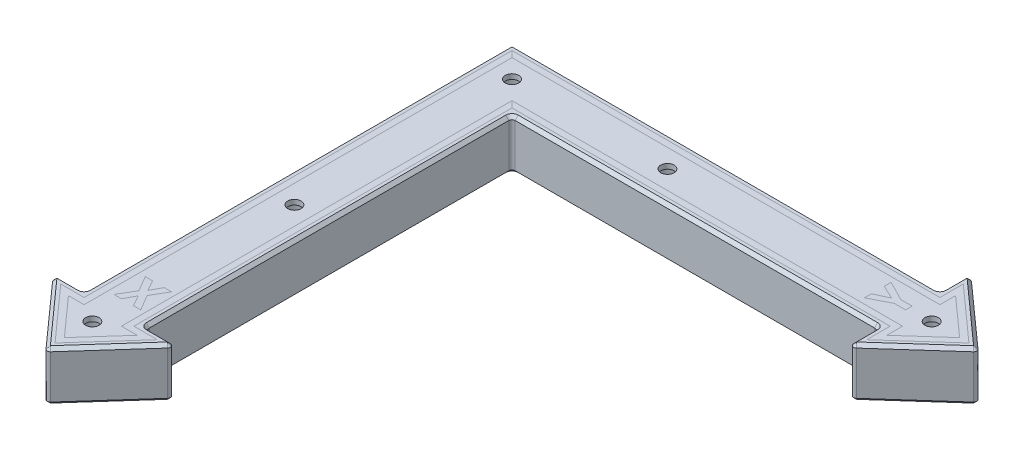
SolidWorks part; units mm, degrees
note: The reader was unsure of these and kept them because the rebuilt part matched: shared geometry of "Sketch4<3>", "Sketch5<2>", "Sketch6<2>", "Sketch7<2>".
ref_plane "Front Plane" through (0, 0, 0) normal (0, 0, 1) x (1, 0, 0)
ref_plane "Top Plane" through (0, 0, 0) normal (0, 1, 0) x (1, 0, 0)
ref_plane "Right Plane" through (0, 0, 0) normal (1, 0, 0) x (0, 0, -1)
sketch "Sketch1" plane through (0, 0, 0) normal (0, 1, 0) x (1, 0, 0)
  line L0 (0, 0) -> (150, 0) construction
  line L1 (0, 0) -> (0, -150) construction
  line L14 (0, -150) -> (20, -127.6393)
  line L15 (20, -127.6393) -> (10, -127.6393)
  line L16 (10, -127.6393) -> (10, -10)
  line L17 (10, -10) -> (127.6393, -10)
  line L18 (127.6393, -10) -> (127.6393, -20)
  line L19 (127.6393, -20) -> (150, 0)
  line L20 (150, 0) -> (127.6393, 20)
  line L21 (127.6393, 20) -> (127.6393, 10)
  line L22 (127.6393, 10) -> (-10, 10)
  line L23 (-10, 10) -> (-10, -127.6393)
  line L24 (-10, -127.6393) -> (-20, -127.6393)
  line L25 (-20, -127.6393) -> (0, -150)
  point P2 (0, 0)
  point P14 (0, 0)
  point P15 (111.1545, 10.3215)
  point P16 (150, 0)
  point P17 (13.8943, -13.8943)
  point P18 (150, 0)
  dimension "D1" = 150
  dimension "D2" = 10
  dimension "D3" = 30
  dimension "D4" = 10
extrude "Boss-Extrude1" add sketch "Sketch1" along normal blind 16
sketch "Sketch2" plane through (0, 16, 0) normal (0, 1, 0) x (1, 0, 0)
  line L0 (0, 0) -> (150, 0) construction
  line L1 (0, -150) -> (0, 0) construction
  circle A0 centre (0, 0) radius 2.15
  circle A1 centre (50, 0) radius 2.15
  circle A2 centre (135, 0) radius 2.15
  circle A3 centre (0, -135) radius 2.15
  circle A4 centre (0, -70) radius 2.15
  point P17 (0, -5.6288)
  dimension "D1" = 4.3
  dimension "D2" = 135
  dimension "D4" = 50
  dimension "D5" = 70
  dimension "D3" = 135
extrude "Cut-Extrude1" cut sketch "Sketch2" against normal through all and the other way through all
sketch "Sketch3" plane through (0, 0, 0) normal (0, -1, 0) x (1, 0, 0)
  circle A0 centre (135, 0) radius 5
  circle A1 centre (50, 0) radius 5
  circle A2 centre (0, 0) radius 5
  circle A3 centre (0, 70) radius 5
  circle A4 centre (0, 135) radius 5
  dimension "D1" = 10
extrude "Cut-Extrude2" cut sketch "Sketch3" against normal offset from surface (14.4 mm away) 1.6 up to face at (0, 16, 67.85)
sketch "Sketch4" plane through (0, 16, 0) normal (0, 1, 0) x (1, 0, 0)
  line L12 (131.6393, 6) -> (-6, 6) construction
  line L13 (-6, 6) -> (-6, -131.6393)
  line L14 (-6, -131.6393) -> (-11.0557, -131.6393)
  line L15 (-11.0557, -131.6393) -> (0, -144)
  line L16 (0, -144) -> (11.0557, -131.6393)
  line L17 (11.0557, -131.6393) -> (6, -131.6393)
  line L18 (6, -131.6393) -> (6, -6)
  line L19 (6, -6) -> (131.6393, -6) construction
  line L20 (131.6393, -6) -> (131.6393, -11.0557) construction
  line L21 (131.6393, -11.0557) -> (144, 0) construction
  line L22 (144, 0) -> (131.6393, 11.0557) construction
  line L23 (131.6393, 11.0557) -> (131.6393, 6) construction
  line L24 (147, 0) -> (129.6393, 15.5279)
  line L25 (129.6393, 15.5279) -> (129.6393, 8)
  line L26 (129.6393, 8) -> (-8, 8)
  line L27 (-8, 8) -> (-8, -129.6393)
  line L28 (-8, -129.6393) -> (-15.5279, -129.6393)
  line L29 (-15.5279, -129.6393) -> (0, -147)
  line L30 (0, -147) -> (15.5279, -129.6393)
  line L31 (15.5279, -129.6393) -> (8, -129.6393)
  line L32 (8, -129.6393) -> (8, -8)
  line L33 (8, -8) -> (129.6393, -8)
  line L34 (129.6393, -8) -> (129.6393, -15.5279)
  line L35 (129.6393, -15.5279) -> (147, 0)
  line L36 (147, 0) -> (129.6393, 15.5279) construction
  line L37 (129.6393, 15.5279) -> (129.6393, 8) construction
  line L38 (129.6393, 8) -> (-8, 8) construction
  line L39 (-8, 8) -> (-8, -129.6393)
  line L40 (-8, -129.6393) -> (-15.5279, -129.6393)
  line L41 (-15.5279, -129.6393) -> (0, -147)
  line L42 (0, -147) -> (15.5279, -129.6393)
  line L43 (15.5279, -129.6393) -> (8, -129.6393)
  line L44 (8, -129.6393) -> (8, -8)
  line L45 (8, -8) -> (129.6393, -8) construction
  line L46 (129.6393, -8) -> (129.6393, -15.5279) construction
  line L47 (129.6393, -15.5279) -> (147, 0) construction
  line L48 (-8, 8) -> (-6, 6)
  line L49 (6, -6) -> (8, -8)
  dimension "D1" = 2
  dimension "D2" = 2
extrude "Cut-Extrude3" cut sketch "Sketch4" against normal blind 1
extrude "Boss-Extrude2" add sketch "Sketch4<3>" against normal up to surface (1 mm away) separate body
sketch "Sketch4<3>" plane through (0, 16, 0) normal (0, 1, 0) x (1, 0, 0) same geometry as "Sketch4"
sketch "Sketch5" plane through (0, 16, 0) normal (0, 1, 0) x (1, 0, 0)
  line L0 (131.6393, 11.0557) -> (131.6393, 6) construction
  line L1 (129.6393, 15.5279) -> (129.6393, 8) construction
  line L2 (147, 0) -> (129.6393, 15.5279) construction
  line L3 (144, 0) -> (131.6393, 11.0557) construction
  line L4 (129.6393, -15.5279) -> (147, 0) construction
  line L5 (131.6393, -11.0557) -> (144, 0) construction
  line L6 (129.6393, -8) -> (129.6393, -15.5279) construction
  line L7 (131.6393, -6) -> (131.6393, -11.0557) construction
  line L8 (8, -8) -> (129.6393, -8) construction
  line L9 (6, -6) -> (131.6393, -6) construction
  line L10 (6, -6) -> (8, -8) construction
  line L11 (129.6393, 8) -> (-8, 8) construction
  line L12 (131.6393, 6) -> (-6, 6) construction
  line L13 (-8, 8) -> (-6, 6) construction
  line L14 (131.6393, 11.0557) -> (131.6393, 6)
  line L15 (129.6393, 15.5279) -> (129.6393, 8)
  line L16 (147, 0) -> (129.6393, 15.5279)
  line L17 (144, 0) -> (131.6393, 11.0557)
  line L18 (129.6393, -15.5279) -> (147, 0)
  line L19 (131.6393, -11.0557) -> (144, 0)
  line L20 (129.6393, -8) -> (129.6393, -15.5279)
  line L21 (131.6393, -6) -> (131.6393, -11.0557)
  line L22 (8, -8) -> (129.6393, -8)
  line L23 (6, -6) -> (131.6393, -6)
  line L24 (6, -6) -> (8, -8)
  line L25 (129.6393, 8) -> (-8, 8)
  line L26 (131.6393, 6) -> (-6, 6)
  line L27 (-8, 8) -> (-6, 6)
extrude "Cut-Extrude4" cut sketch "Sketch5" against normal blind 1
extrude "Boss-Extrude3" add sketch "Sketch5<2>" against normal up to surface (1 mm away) separate body up to face at (55.4631, 15, 55.4631)
sketch "Sketch5<2>" plane through (0, 16, 0) normal (0, 1, 0) x (1, 0, 0) same geometry as "Sketch5"
fillet "Fillet1" radius 1 12 edges at (-10, 8, -10) (127.6393, 8, -20) (150, 8, 0) (127.6393, 8, 20) (0, 8, 150) (-20, 8, 127.6393) (20, 8, 127.6393) (127.6393, 8, 10) (127.6393, 8, -10) (-10, 8, 127.6393) (10, 8, 127.6393) (10, 8, 10)
chamfer "Chamfer1" distance 1 angle 45 48 edges at (10, 16, 68.8197) (10.2929, 16, 10.2929) (10.2929, 16, 127.3464) (68.8197, 16, 10) (14.382, 16, 127.6393) (127.3464, 16, 10.2929) (18.6768, 16, 128.2311) (127.6393, 16, 14.382) (9.6273, 16, 139.2363) (128.2311, 16, 18.6768) (0, 16, 149.5) (139.2363, 16, 9.6273) (-9.6273, 16, 139.2363) (149.5, 16, 0) (-18.6768, 16, 128.2311) (139.2363, 16, -9.6273) (-14.382, 16, 127.6393) (128.2311, 16, -18.6768) (-10.2929, 16, 127.3464) (127.6393, 16, -14.382) (-10, 16, 58.8197) (127.3464, 16, -10.2929) (-9.7071, 16, -9.7071) (58.8197, 16, -10) (68.8197, 0, 10) (127.3464, 0, 10.2929) (10.2929, 0, 10.2929) (127.6393, 0, 14.382) (10, 0, 68.8197) (128.2311, 0, 18.6768) (10.2929, 0, 127.3464) (139.2363, 0, 9.6273) (14.382, 0, 127.6393) (149.5, 0, 0) (18.6768, 0, 128.2311) (139.2363, 0, -9.6273) (9.6273, 0, 139.2363) (128.2311, 0, -18.6768) (0, 0, 149.5) (127.6393, 0, -14.382) (-9.6273, 0, 139.2363) (127.3464, 0, -10.2929) (-18.6768, 0, 128.2311) (58.8197, 0, -10) (-14.382, 0, 127.6393) (-9.7071, 0, -9.7071) (-10.2929, 0, 127.3464) (-10, 0, 58.8197)
sketch "Sketch6" plane through (0, 16, 0) normal (0, 1, 0) x (1, 0, 0)
  line L0 (-4.2, -124) -> (3.6894, -124) construction
  text T0 "X" font "Roboto" height 10
  dimension "D1" = 20
  dimension "D2" = 4.2
extrude "Cut-Extrude5" cut sketch "Sketch6" against normal blind 1
extrude "Boss-Extrude4" add sketch "Sketch6<2>" against normal up to surface (1 mm away) separate body up to face at (0.2584, 15, 118.9887)
sketch "Sketch6<2>" plane through (0, 16, 0) normal (0, 1, 0) x (1, 0, 0) same geometry as "Sketch6"
sketch "Sketch7" plane through (0, 16, 0) normal (0, 1, 0) x (1, 0, 0)
  line L0 (127.5832, -4.2468) -> (127.5832, 4.0942) construction
  text T0 "Y" font "Roboto" height 10
extrude "Cut-Extrude6" cut sketch "Sketch7" against normal blind 1
extrude "Boss-Extrude5" add sketch "Sketch7<2>" against normal up to surface (1 mm away) separate body up to face at (121.7224, 15, -0.0854)
sketch "Sketch7<2>" plane through (0, 16, 0) normal (0, 1, 0) x (1, 0, 0) same geometry as "Sketch7"
chamfer "Chamfer2" distance 1 angle 45 5 edges at (0, 0, 130) (0, 0, 65) (0, 0, -5) (50, 0, -5) (135, 0, -5)
